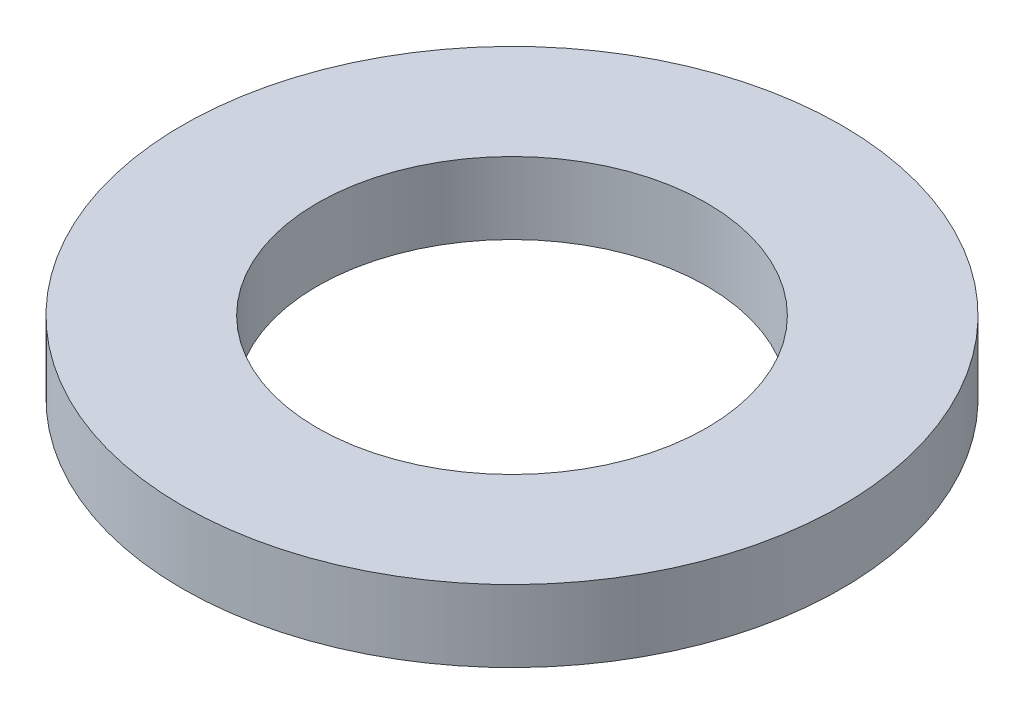
SolidWorks part; units mm, degrees
ref_plane "Front Plane" through (0, 0, 0) normal (0, 0, 1) x (1, 0, 0)
ref_plane "Top Plane" through (0, 0, 0) normal (0, 1, 0) x (1, 0, 0)
ref_plane "Right Plane" through (0, 0, 0) normal (1, 0, 0) x (0, 0, -1)
sketch "Sketch1" plane through (0, 0, 0) normal (0, 1, 0) x (1, 0, 0)
  circle A0 centre (0, 0) radius 55
  dimension "FLANGE_OD" = 110
extrude "Boss-Extrude1" add sketch "Sketch1" along normal blind 12
sketch "Sketch2" plane through (0, 0, 0) normal (0, 1, 0) x (1, 0, 0)
  circle A0 centre (0, 0) radius 32.5
  dimension "BORE_D" = 65
extrude "Cut-Extrude1" cut sketch "Sketch2" along normal through all
sketch "Sketch3" plane through (0, 12, 0) normal (0, 1, 0) x (1, 0, 0)
  circle A0 centre (0, 0) radius 18.2209 construction
  circle A1 centre (-18.2209, 0) radius 1.9528
  dimension "BOLT_D" = 3.9056
  dimension "BOLT_PCD" = 36.4418
extrude "Cut-Extrude2" cut sketch "Sketch3" against normal blind 7.9244 rebuild error yes
pattern_circular "CirPattern1" count 5 over 360 rebuild error yes
